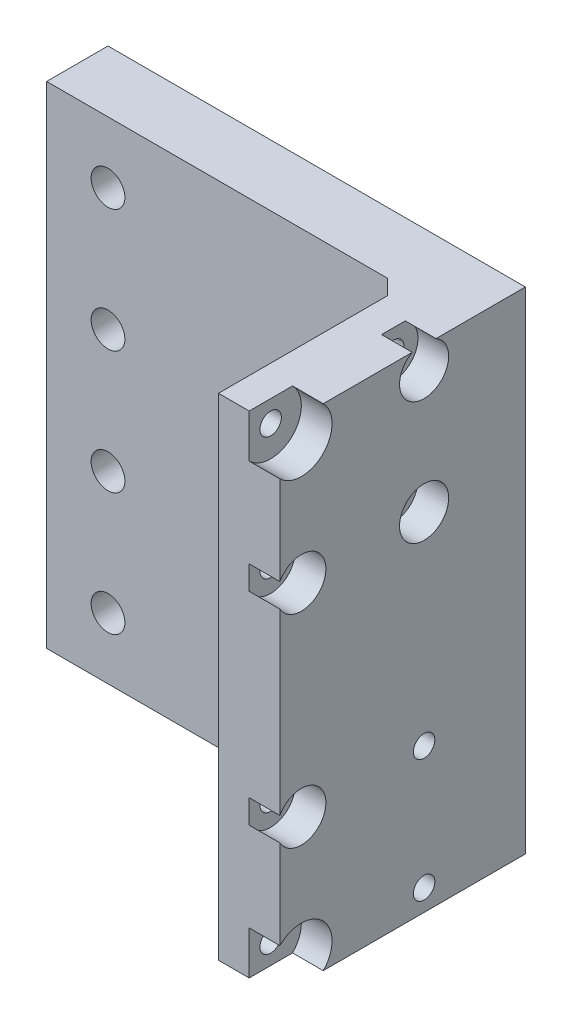
SolidWorks part; units mm, degrees
ref_plane "Plan de face" through (0, 0, 0) normal (0, 0, 1) x (1, 0, 0)
ref_plane "Plan de dessus" through (0, 0, 0) normal (0, 1, 0) x (1, 0, 0)
ref_plane "Plan de droite" through (0, 0, 0) normal (1, 0, 0) x (0, 0, -1)
sketch "Esquisse1" plane through (0, 0, 0) normal (0, 0, 1) x (1, 0, 0)
  line L1 (-33.3969, 24.3516) -> (34.6031, 24.3516)
  line L2 (-33.3969, 24.3516) -> (-33.3969, -55.6484)
  line L3 (-33.3969, -55.6484) -> (34.6031, -55.6484)
  line L4 (34.6031, 24.3516) -> (34.6031, -55.6484)
  circle A0 centre (-23.3969, 14.3516) radius 2.75
  circle A1 centre (-23.3969, -5.6484) radius 2.75
  circle A2 centre (-23.3969, -25.6484) radius 2.75
  circle A3 centre (-23.3969, -45.6484) radius 2.75
  dimension "D3" = 5.5
  dimension "D1" = 80
  dimension "D2" = 68
  dimension "D4" = 10
  dimension "D5" = 10
  dimension "D6" = 20
  dimension "D7" = 20
  dimension "D8" = 10
extrude "Boss.-Extru.1" add sketch "Esquisse1" along normal blind 10
sketch "Esquisse2" plane through (0, 0, 10) normal (0, 0, -1) x (-1, 0, 0)
  line L0 (-34.6031, 24.3516) -> (33.3969, 24.3516) construction
  line L1 (-34.6031, -55.6484) -> (-24.6031, -55.6484)
  line L2 (-34.6031, -55.6484) -> (-34.6031, 24.3516)
  line L3 (-34.6031, 24.3516) -> (-24.6031, 24.3516)
  line L4 (-24.6031, -55.6484) -> (-24.6031, 24.3516)
  dimension "D1" = 10
extrude "Boss.-Extru.2" add sketch "Esquisse2" against normal blind 30
sketch "Esquisse3" plane through (34.6031, 0, 0) normal (1, 0, 0) x (0, 0, -1)
  line L0 (-16.5, -52.1484) -> (-36.5, -52.1484) construction
  line L1 (-36.5, -52.1484) -> (-36.5, -32.1484) construction
  line L2 (-36.5, 20.8516) -> (-16.5, 20.8516) construction
  line L3 (-16.5, 20.8516) -> (-16.5, 0.8516) construction
  line L4 (-40, 24.3516) -> (-40, -55.6484) construction
  line L5 (-40, -55.6484) -> (0, -55.6484) construction
  line L6 (-40, 24.3516) -> (0, 24.3516) construction
  circle A0 centre (-36.5, -52.1484) radius 1.75
  circle A1 centre (-36.5, -32.1484) radius 1.75
  circle A2 centre (-16.5, -32.1484) radius 1.75
  circle A3 centre (-16.5, -52.1484) radius 1.75
  circle A4 centre (-36.5, 0.8516) radius 1.75
  circle A5 centre (-36.5, 20.8516) radius 1.75
  circle A6 centre (-16.5, 20.8516) radius 1.75
  circle A7 centre (-16.5, 0.8516) radius 1.75
  dimension "D1" = 3.5
  dimension "D2" = 20
  dimension "D3" = 3.5
  dimension "D4" = 3.5
  dimension "D5" = 3.5
extrude "Enlèv. mat.-Extru.1" cut sketch "Esquisse3" against normal up to next
sketch "Esquisse5" plane through (34.6031, 0, 0) normal (1, 0, 0) x (0, 0, -1)
  circle A0 centre (-36.5, -52.1484) radius 5
  circle A1 centre (-36.5, -32.1484) radius 4
  circle A2 centre (-36.5, 0.8516) radius 4
  circle A3 centre (-36.5, 20.8516) radius 5
  circle A4 centre (-16.5, 20.8516) radius 4
  circle A5 centre (-16.5, 0.8516) radius 4
  dimension "D1" = 10
  dimension "D2" = 8
extrude "Enlèv. mat.-Extru.3" cut sketch "Esquisse5" against normal blind 5
sketch "Esquisse4" plane through (0, 0, 0) normal (0, 0, -1) x (-1, 0, 0)
  circle A0 centre (23.3969, -45.6484) radius 6
  circle A1 centre (23.3969, -25.6484) radius 6
  circle A2 centre (23.3969, -5.6484) radius 6
  circle A3 centre (23.3969, 14.3516) radius 6
  dimension "D1" = 12
extrude "Enlèv. mat.-Extru.2" cut sketch "Esquisse4" against normal blind 5
chamfer "Chanfrein1" distance 2.5 angle 45 1 edges at (24.6031, -15.6484, 10)
